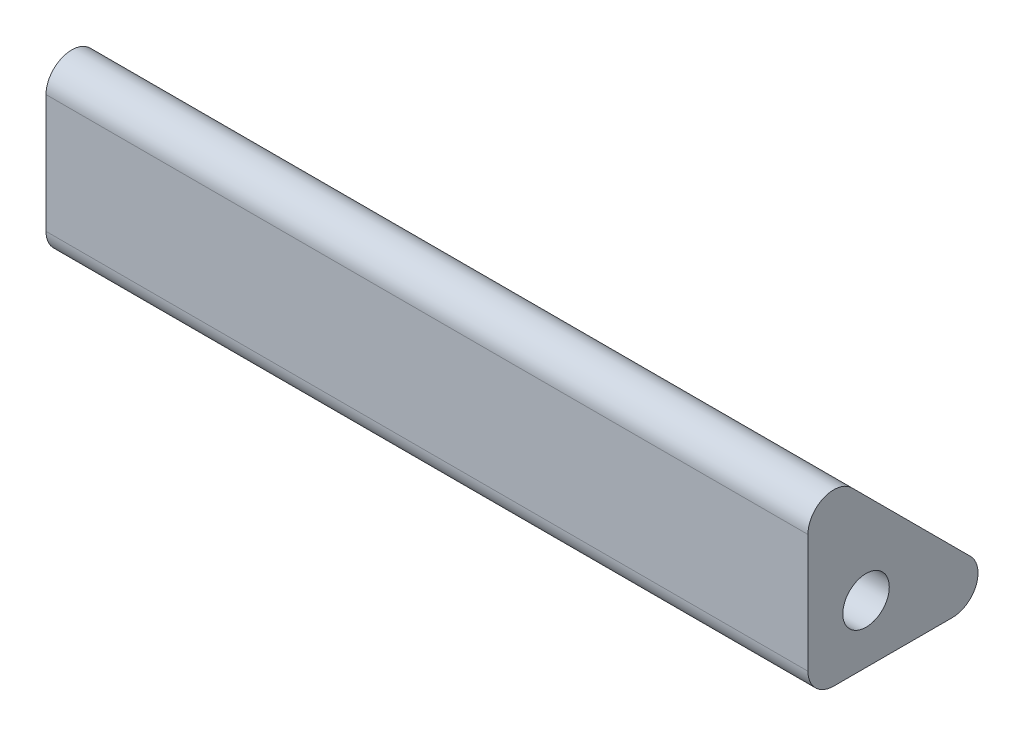
SolidWorks part; units mm, degrees
ref_plane "Front Plane" through (0, 0, 0) normal (0, 0, 1) x (1, 0, 0)
ref_plane "Top Plane" through (0, 0, 0) normal (0, 1, 0) x (1, 0, 0)
ref_plane "Right Plane" through (0, 0, 0) normal (1, 0, 0) x (0, 0, -1)
sketch "Sketch1" plane through (0, 0, 0) normal (1, 0, 0) x (0, 0, -1)
  line L0 (-2.25, 5.75) -> (-2.25, -2.25)
  line L1 (-2.25, -2.25) -> (5.75, -2.25)
  line L3 (-2.25, 5.75) -> (5.75, -2.25)
  circle A0 centre (0, 0) radius 0.9
  dimension "D1" = 1.8
  dimension "D2" = 8
  dimension "D3" = 8
  dimension "D4" = 2.25
  dimension "D5" = 2.25
extrude "Boss-Extrude1" add sketch "Sketch1" along normal blind 29.5
fillet "Fillet1" radius 1 3 edges at (14.75, -2.25, 2.25) (14.75, -2.25, -5.75) (14.75, 5.75, 2.25)
